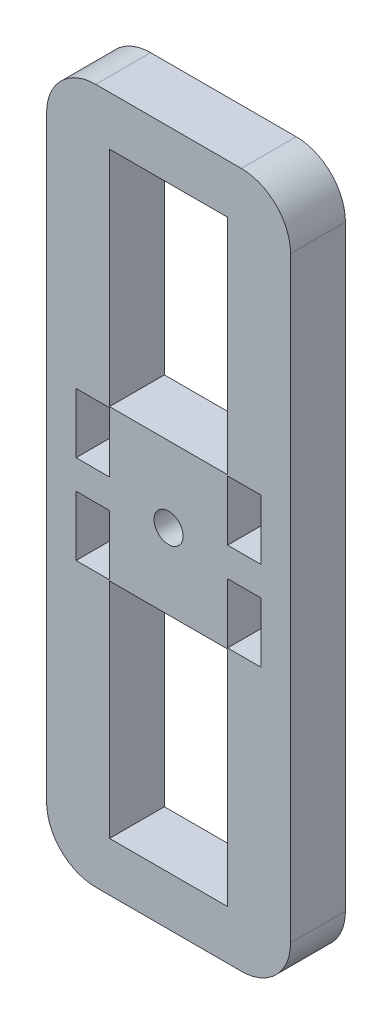
SolidWorks part; units mm, degrees
material "Acrylic (Medium-high impact)"
ref_plane "Front Plane" through (0, 0, 0) normal (0, 0, 1) x (1, 0, 0)
ref_plane "Top Plane" through (0, 0, 0) normal (0, 1, 0) x (1, 0, 0)
ref_plane "Right Plane" through (0, 0, 0) normal (1, 0, 0) x (0, 0, -1)
sketch "Sketch1" plane through (0, 0, 0) normal (0, 0, 1) x (1, 0, 0)
  line L0 (709.6957, 498.2992) -> (721.6957, 498.2992)
  line L1 (721.6957, 498.2992) -> (721.6957, 475.6297)
  line L2 (721.6957, 475.6297) -> (709.6957, 475.6297)
  line L3 (709.6957, 475.6297) -> (709.6957, 498.2992)
  line L4 (715.6957, 432.6102) -> (723.0957, 432.6102)
  line L5 (715.6957, 503.2992) -> (708.2957, 503.2992)
  line L6 (715.6957, 503.2992) -> (723.0957, 503.2992)
  line L7 (715.6957, 460.2797) -> (715.6957, 475.6297) construction
  line L8 (709.6957, 498.2992) -> (703.2957, 498.2992) construction
  line L9 (721.6957, 498.2992) -> (728.0957, 498.2992) construction
  line L10 (709.6957, 475.5297) -> (706.2957, 475.5297)
  line L11 (728.0957, 498.2992) -> (728.0957, 437.6102)
  line L12 (709.6957, 475.5297) -> (709.6957, 469.4297)
  line L13 (709.6957, 469.4297) -> (706.2957, 469.4297)
  line L14 (706.2957, 469.4297) -> (706.2957, 475.5297)
  line L15 (703.2957, 498.2992) -> (703.2957, 437.6102)
  line L16 (721.6957, 475.5297) -> (725.0957, 475.5297)
  line L17 (725.0957, 469.4297) -> (725.0957, 475.5297)
  line L18 (721.6957, 469.4297) -> (725.0957, 469.4297)
  line L19 (721.6957, 475.5297) -> (721.6957, 469.4297)
  line L20 (721.6957, 460.3797) -> (725.0957, 460.3797)
  line L21 (725.0957, 466.4797) -> (725.0957, 460.3797)
  line L22 (715.6957, 432.6102) -> (708.2957, 432.6102)
  line L24 (721.6957, 466.4797) -> (725.0957, 466.4797)
  line L25 (721.6957, 460.3797) -> (721.6957, 466.4797)
  line L26 (709.6957, 460.3797) -> (706.2957, 460.3797)
  line L27 (706.2957, 466.4797) -> (706.2957, 460.3797)
  line L28 (709.6957, 466.4797) -> (706.2957, 466.4797)
  line L29 (709.6957, 460.3797) -> (709.6957, 466.4797)
  line L30 (-282.9616, 469.4297) -> (49717.0384, 469.4297) construction
  line L31 (-282.9616, 466.4797) -> (49717.0384, 466.4797) construction
  line L37 (709.6957, 460.2797) -> (709.6957, 437.6102)
  line L38 (721.6957, 460.2797) -> (709.6957, 460.2797)
  line L39 (721.6957, 437.6102) -> (721.6957, 460.2797)
  line L40 (709.6957, 437.6102) -> (721.6957, 437.6102)
  line L171 (-296.4722, 467.9547) -> (49703.5278, 467.9547) construction
  circle A0 centre (715.6957, 467.9547) radius 1.475
  arc A1 (708.2957, 432.6102) -> (703.2957, 437.6102) centre (708.2957, 437.6102) cw
  arc A2 (708.2957, 503.2992) -> (703.2957, 498.2992) centre (708.2957, 498.2992) ccw
  arc A3 (723.0957, 503.2992) -> (728.0957, 498.2992) centre (723.0957, 498.2992) cw
  arc A4 (723.0957, 432.6102) -> (728.0957, 437.6102) centre (723.0957, 437.6102) ccw
  point P6 (715.6957, 504.6992)
  point P33 (715.6957, 475.6297)
  point P37 (715.6957, 467.9547)
  point P46 (715.6957, 431.2102)
  dimension "D1" = 6.1
  dimension "D4" = 2.95
  dimension "D2" = 3.4
  dimension "D3" = 0.1
  dimension "D7" = 3
  dimension "D8" = 5
extrude "Boss-Extrude1" add sketch "Sketch1" along normal blind 5.58 contours L2 L3 L0 L1 L40 L37 L38 L39 A0 region at (711.9957, 433.3593, 0)
